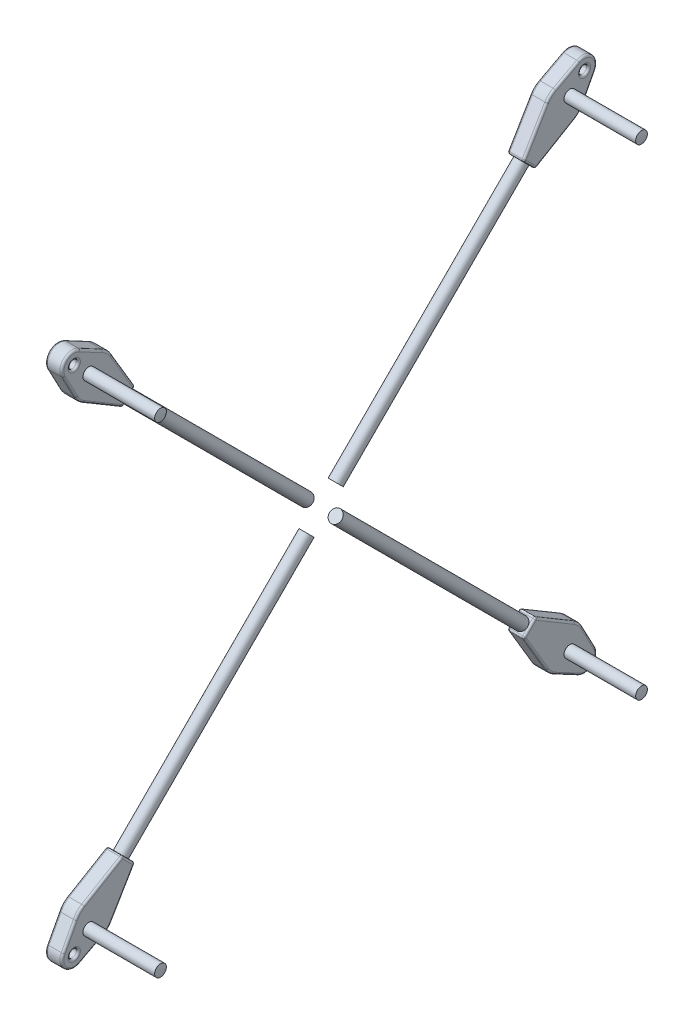
SolidWorks part; units mm, degrees
ref_plane "Plan de face" through (0, 0, 0) normal (0, 0, 1) x (1, 0, 0)
ref_plane "Plan de dessus" through (0, 0, 0) normal (0, 1, 0) x (1, 0, 0)
ref_plane "Plan de droite" through (0, 0, 0) normal (1, 0, 0) x (0, 0, -1)
sketch "Esquisse4" plane through (0, 0, 0) normal (0, 0, 1) x (1, 0, 0)
  line L0 (0, 0) -> (44.4377, 0) construction
sketch "Esquisse5" plane through (0, 0, 0) normal (1, 0, 0) x (0, 0, -1)
  line L0 (0, 0) -> (-163.9371, 163.9371) construction
ref_axis "Axe1" through (0, 0, 0) along (0, 0.7071, 0.7071)
ref_axis "Axe2" through (0, 0, 0) along (0, 0.7071, 0.7071)
ref_plane "Plan1" through (0, 0, 0) normal (0, 0.7071, 0.7071) x (1, 0, 0)
ref_plane "Plan2" through (0, 7.0711, 7.0711) normal (0, 0.7071, 0.7071) x (1, 0, 0)
ref_plane "Plan3" through (0, 0, 0) normal (0, -0.7071, 0.7071) x (1, 0, 0)
sketch "Esquisse6" plane through (0, 7.0711, 7.0711) normal (0, 0.7071, 0.7071) x (1, 0, 0)
  circle A0 centre (0, 0) radius 3
  dimension "D1" = 6
extrude "Boss.-Extru.1" add sketch "Esquisse6" along normal blind 155
sketch "Esquisse7" plane through (0, 0, 0) normal (1, 0, 0) x (0, 0, -1)
  line L0 (-100.1055, 94.1531) -> (-94.1531, 100.1055)
  line L1 (0, 0) -> (-163.9371, 163.9371) construction
  line L2 (-94.1531, 100.1055) -> (-105.4789, 119.1951)
  line L3 (-114.0876, 114.0876) -> (-150.9556, 150.9556) construction
  line L4 (-100.1055, 94.1531) -> (-119.1951, 105.4789)
  line L5 (0, 0) -> (-163.9371, 163.9371) construction
  line L6 (-129.045, 120.9337) -> (-122.9706, 109.4737)
  line L7 (-120.8736, 129.0127) -> (-109.8427, 123.1527)
  arc A0 (-120.8736, 129.0127) -> (-129.045, 120.9337) centre (-123.7437, 123.7437) ccw
  arc A1 (-105.4789, 119.1951) -> (-109.8427, 123.1527) centre (-114.0876, 114.0876) ccw
  arc A2 (-122.9706, 109.4737) -> (-119.1951, 105.4789) centre (-114.0876, 114.0876) ccw
  point P10 (-97.1293, 97.1293)
  dimension "D1" = 175
  dimension "D2" = 6
extrude "Boss.-Extru.2" add sketch "Esquisse7" along normal blind 4 and the other way blind 5.5
sketch "Esquisse8" plane through (0, 0, 0) normal (1, 0, 0) x (0, 0, -1)
  circle A0 centre (-123.7437, 123.7437) radius 2
  dimension "D1" = 4
extrude "Enlèv. mat.-Extru.1" cut sketch "Esquisse8" against normal mid plane 42
sketch "Esquisse10" plane through (-5.5, 0, 0) normal (-1, 0, 0) x (0, 0, 1)
  line L1 (84.422, 135.8521) -> (141.5246, 135.8521)
  line L2 (84.422, 135.8521) -> (84.422, 92.8922)
  line L3 (84.422, 92.8922) -> (141.5246, 92.8922)
  line L4 (141.5246, 135.8521) -> (141.5246, 92.8922)
  circle A0 centre (123.7437, 123.7437) radius 3.0002
extrude "Enlèv. mat.-Extru.3" cut sketch "Esquisse10" against normal blind 1.5
fillet "Congé1" radius 1 18 edges at (-4, 123.7437, 126.7438) (-4, 97.1293, 97.1293) (-4, 109.6503, 99.816) (-4, 121.5022, 107.3631) (-4, 126.0827, 115.3581) (-4, 128.0104, 127.9621) (-4, 115.2037, 126.0078) (-4, 107.2121, 121.3624) (-4, 99.816, 109.6503) (4, 97.1293, 97.1293) (4, 99.816, 109.6503) (4, 107.2121, 121.3624) (4, 115.2037, 126.0078) (4, 128.0104, 127.9621) (4, 126.0827, 115.3581) (4, 121.5022, 107.3631) (4, 109.6503, 99.816) (4, 123.7437, 121.7437)
fillet "Congé2" radius 1 6 edges at (-3.7071, 100.1517, 94.5211) (3.7071, 100.1517, 94.5211) (-3.7071, 94.5211, 100.1517) (3.7071, 94.5211, 100.1517) (0, 100.1055, 94.1531) (0, 94.1531, 100.1055)
sketch "Esquisse12" plane through (0, 0, 0) normal (0, -0.7071, 0.7071) x (1, 0, 0)
  line L0 (4, 176.468) -> (4, 164.0652) construction
  line L1 (4, 167.8194) -> (38.7662, 167.8194)
  line L2 (4, 167.8194) -> (4, 164.9684)
  line L3 (4, 164.9684) -> (39, 164.9684)
  line L5 (4, 164.9684) -> (45.9762, 164.9684) construction
  arc A0 (38.7662, 167.8194) -> (39, 164.9684) centre (21.5, 164.9684) cw
  dimension "D1" = 35
  dimension "D2" = 2.851
revolve "Révolution1" add sketch "Esquisse12" angle 360 about L5
pattern_circular "Répétition circulaire5" count 4 over 360 about axis through (0, 0, 0) along (1, 0, 0) reverse direction yes of bodies 113 107
